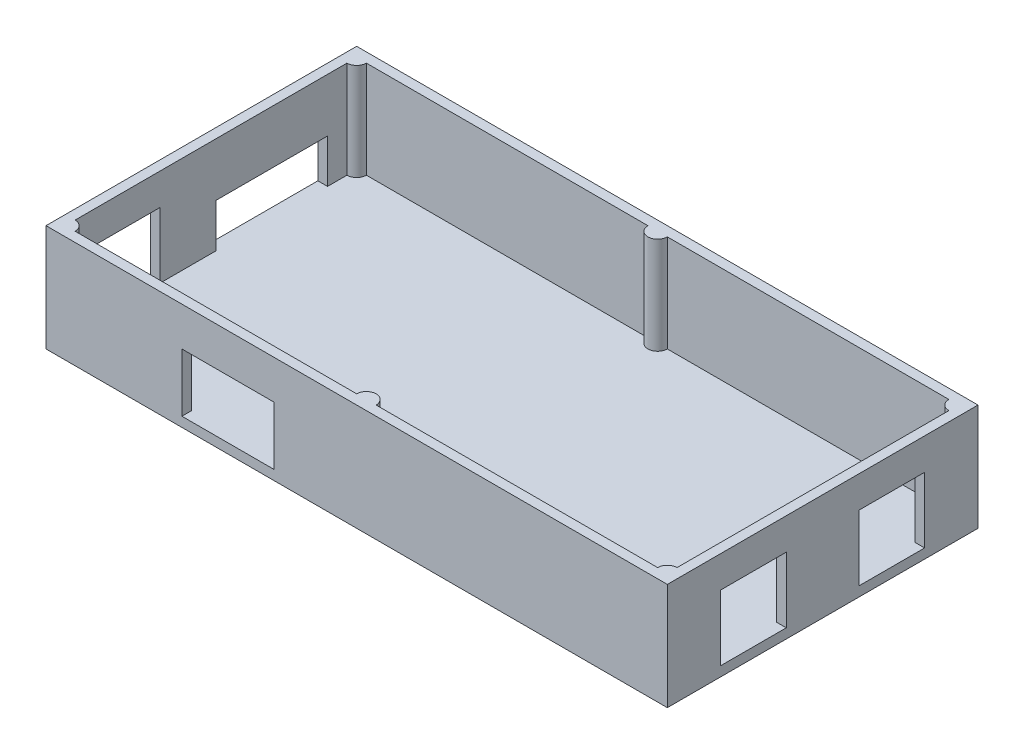
SolidWorks part; units mm, degrees
ref_plane "Front Plane" through (0, 0, 0) normal (0, 0, 1) x (1, 0, 0)
ref_plane "Top Plane" through (0, 0, 0) normal (0, 1, 0) x (1, 0, 0)
ref_plane "Right Plane" through (0, 0, 0) normal (1, 0, 0) x (0, 0, -1)
sketch "Sketch3" plane through (0, 0, 0) normal (0, 1, 0) x (1, 0, 0)
  line L0 (64, 32) -> (-64, 32)
  line L3 (60, 30) -> (2, 30)
  line L4 (-62, -28) -> (-62, 28)
  line L5 (62, -30) -> (-62, 30) construction
  line L6 (62, 30) -> (-62, -30) construction
  line L7 (-64, -32) -> (-64, 32)
  line L8 (64, -32) -> (-64, -32)
  line L9 (64, -32) -> (64, 32)
  line L10 (0, 30) -> (0, -6) construction
  line L11 (-62, 0) -> (62, 0) construction
  line L12 (62, -28) -> (62, 28)
  line L13 (62, 30) -> (-62, 30) construction
  line L14 (-62, -30) -> (-62, 30) construction
  line L15 (62, -30) -> (62, 30) construction
  line L16 (62, -30) -> (-62, -30) construction
  line L18 (-2, 30) -> (-60, 30)
  line L19 (60, -30) -> (2, -30)
  line L20 (-2, -30) -> (-60, -30)
  line L21 (0, -32) -> (0, -52) construction
  line L22 (0, -52) -> (-27.8375, -52) construction
  line L23 (-62, -104) -> (62, -104) construction
  line L32 (0, -134) -> (0, -98) construction
  line L33 (62, -134) -> (-62, -74) construction
  line L34 (62, -74) -> (-62, -134) construction
  line L35 (-2, -74) -> (-60, -74)
  line L36 (60, -74) -> (2, -74)
  line L37 (-2, -134) -> (-60, -134)
  line L38 (62, -76) -> (62, -132)
  line L39 (64, -72) -> (64, -136)
  line L40 (64, -72) -> (-64, -72)
  line L41 (-64, -72) -> (-64, -136)
  line L42 (-62, -76) -> (-62, -132)
  line L43 (60, -134) -> (2, -134)
  line L44 (64, -136) -> (-64, -136)
  line L45 (-2.8284, -75) -> (-59.1716, -75)
  line L46 (59.1716, -75) -> (2.8284, -75)
  line L47 (61, -76.8284) -> (61, -131.1716)
  line L48 (59.1716, -133) -> (2.8284, -133)
  line L49 (-2.8284, -133) -> (-59.1716, -133)
  line L50 (-61, -76.8284) -> (-61, -131.1716)
  arc A0 (-62, 28) -> (-60, 30) centre (-62, 30) ccw
  arc A1 (62, 28) -> (60, 30) centre (62, 30) cw
  arc A2 (62, -28) -> (60, -30) centre (62, -30) ccw
  arc A3 (-62, -28) -> (-60, -30) centre (-62, -30) cw
  arc A8 (2, 30) -> (-2, 30) centre (0, 30) cw
  arc A9 (2, -30) -> (-2, -30) centre (0, -30) ccw
  arc A10 (2, -74) -> (-2, -74) centre (0, -74) cw
  arc A11 (2, -134) -> (-2, -134) centre (0, -134) ccw
  arc A12 (-62, -76) -> (-60, -74) centre (-62, -74) ccw
  arc A13 (62, -76) -> (60, -74) centre (62, -74) cw
  arc A14 (62, -132) -> (60, -134) centre (62, -134) ccw
  arc A15 (-62, -132) -> (-60, -134) centre (-62, -134) cw
  arc A16 (-61, -76.8284) -> (-59.1716, -75) centre (-62, -74) ccw
  arc A17 (2.8284, -75) -> (-2.8284, -75) centre (0, -74) cw
  arc A18 (61, -76.8284) -> (59.1716, -75) centre (62, -74) cw
  arc A19 (61, -131.1716) -> (59.1716, -133) centre (62, -134) ccw
  arc A20 (2.8284, -133) -> (-2.8284, -133) centre (0, -134) ccw
  arc A21 (-61, -131.1716) -> (-59.1716, -133) centre (-62, -134) cw
  point P0 (0, 0)
  point P52 (0, -104)
  dimension "D4" = 2
  dimension "D5" = 2
  dimension "D1" = 124
  dimension "D2" = 60
  dimension "D6" = 62
  dimension "D7" = 20
  dimension "D3" = 2
  dimension "D8" = 1
extrude "Boss-Extrude1" add sketch "Sketch3" along normal blind 22 contours L8 L9 L0 L7 L19 A9 L20 A3 L4 A0 L18 A8 L3 A1 L12 A2 region at (62.5689, 0, 0)
extrude "Boss-Extrude3" add sketch "Sketch3<5>" along normal blind 2 contours L4 A3 A2 L12 A1 L3 A0 region at (0, 0, 0)
sketch "Sketch3<5>" plane through (0, 0, 0) normal (0, 1, 0) x (1, 0, 0) same geometry as "Sketch3"
sketch "Sketch5" plane through (64, 0, 0) normal (1, 0, 0) x (0, 0, -1)
  line L0 (0, 0) -> (0, 2) construction
  line L1 (-32, 0) -> (32, 0) construction
  line L2 (0, 2) -> (-28, 2) construction
  line L3 (-28, 2) -> (-28, 17.2402) construction
  line L4 (-32, 22) -> (-32, 0) construction
  line L5 (7.5, 2) -> (7.5, 15.5)
  line L6 (-21, 2) -> (-7.5, 2)
  line L7 (-21, 2) -> (-21, 15.5)
  line L8 (-21, 15.5) -> (-7.5, 15.5)
  line L9 (-7.5, 2) -> (-7.5, 15.5)
  line L10 (21, 15.5) -> (7.5, 15.5)
  line L11 (21, 2) -> (21, 15.5)
  line L12 (21, 2) -> (7.5, 2)
  line L13 (-7.5, 15.5) -> (7.5, 15.5) construction
  dimension "D1" = 2
  dimension "D2" = 4
  dimension "D3" = 13.5
  dimension "D4" = 13.5
  dimension "D5" = 7
extrude "Cut-Extrude1" cut sketch "Sketch5" against normal up to next
sketch "Sketch6" plane through (-64, 0, 0) normal (-1, 0, 0) x (0, 0, 1)
  line L0 (32, 0) -> (-32, 0) construction
  line L1 (-32, 22) -> (-32, 0) construction
  line L2 (24, 15.5) -> (32, 15.5) construction
  line L3 (32, 22) -> (32, 0) construction
  line L4 (-28, 12.1152) -> (-28, 2) construction
  line L5 (-28, 2) -> (0, 2) construction
  line L6 (-24, 20) -> (24, 20) construction
  line L7 (-24, 2) -> (-1, 2)
  line L8 (-24, 2) -> (-24, 11)
  line L9 (-24, 11) -> (-1, 11)
  line L10 (-1, 2) -> (-1, 11)
  line L11 (10.5, 2) -> (24, 2)
  line L12 (10.5, 2) -> (10.5, 15.5)
  line L13 (10.5, 15.5) -> (24, 15.5)
  line L14 (24, 2) -> (24, 15.5)
  line L15 (-32, 22) -> (32, 22) construction
  dimension "D1" = 4
  dimension "D2" = 2
  dimension "D3" = 23
  dimension "D4" = 9
  dimension "D5" = 13.5
  dimension "D6" = 13.5
  dimension "D7" = 48
  dimension "D8" = 2
  dimension "D9" = 8
extrude "Cut-Extrude2" cut sketch "Sketch6" against normal blind 2
sketch "Sketch7" plane through (0, 0, 32) normal (0, 0, 1) x (1, 0, 0)
  line L0 (0, 0) -> (0, 2) construction
  line L1 (0, 2) -> (-60, 2) construction
  line L2 (-60, 2) -> (-60, 13.8865) construction
  line L3 (-64, 22) -> (-64, 0) construction
  line L5 (-36, 2) -> (-17, 2)
  line L6 (-36, 2) -> (-36, 14)
  line L7 (-36, 14) -> (-17, 14)
  line L8 (-17, 2) -> (-17, 14)
  dimension "D1" = 4
  dimension "D2" = 2
  dimension "D3" = 28
  dimension "D4" = 19
  dimension "D5" = 12
extrude "Cut-Extrude3" cut sketch "Sketch7" against normal blind 2
